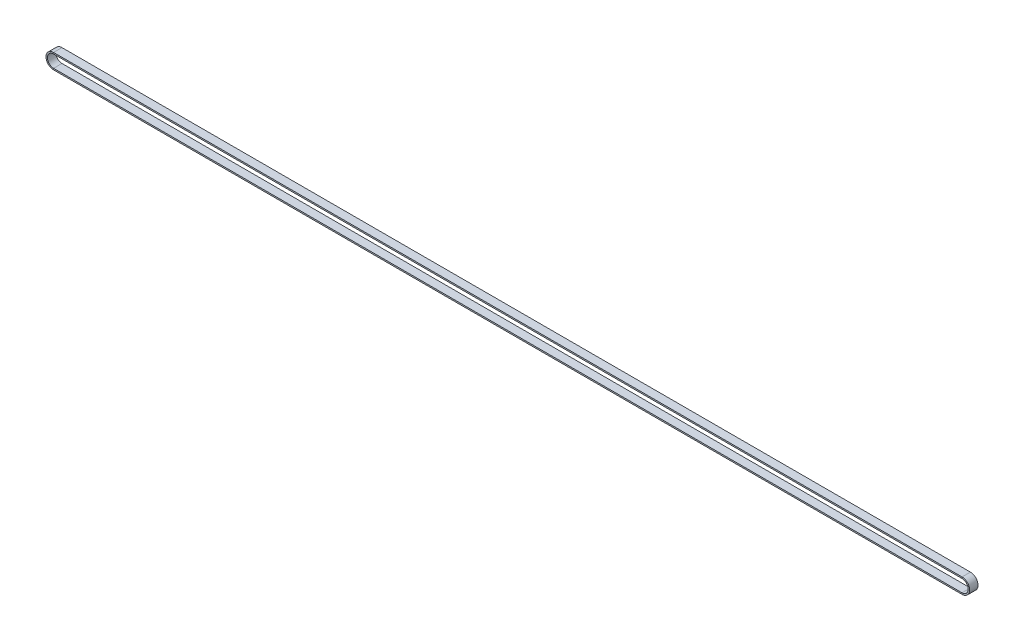
SolidWorks part; units mm, degrees
ref_plane "Front Plane" through (0, 0, 0) normal (0, 0, 1) x (1, 0, 0)
ref_plane "Top Plane" through (0, 0, 0) normal (0, 1, 0) x (1, 0, 0)
ref_plane "Right Plane" through (0, 0, 0) normal (1, 0, 0) x (0, 0, -1)
sketch "Sketch2" plane through (0, 0, 0) normal (0, 0, 1) x (1, 0, 0)
  line L0 (0, 0) -> (1, 0) construction
  line L1 (0, 0) -> (0, 1) construction
  line L2 (-0.0001, 48.4725) -> (-976.331, 48.4725)
  line L3 (-976.331, 64.752) -> (-0.0001, 64.752)
  arc A0 (-0.0001, 64.752) -> (-0.0001, 48.4725) centre (-0.0001, 56.6122) cw
  arc A1 (-976.331, 48.4725) -> (-976.331, 64.752) centre (-976.331, 56.6122) cw
ref_plane "Plane1" through (-0.0001, 64.752, 0) normal (1, 0, 0) x (0, 0, -1)
sketch "Sketch3" plane through (-0.0001, 64.752, 0) normal (1, 0, 0) x (0, 0, -1)
  line L1 (0, -1.5) -> (9, -1.5)
  line L2 (0, -1.5) -> (0, 0)
  line L3 (0, 0) -> (9, 0)
  line L4 (9, -1.5) -> (9, 0)
  dimension "D1" = 1.5
  dimension "D2" = 9
sweep "Sweep1" add profiles "Sketch3" path "Sketch2"
